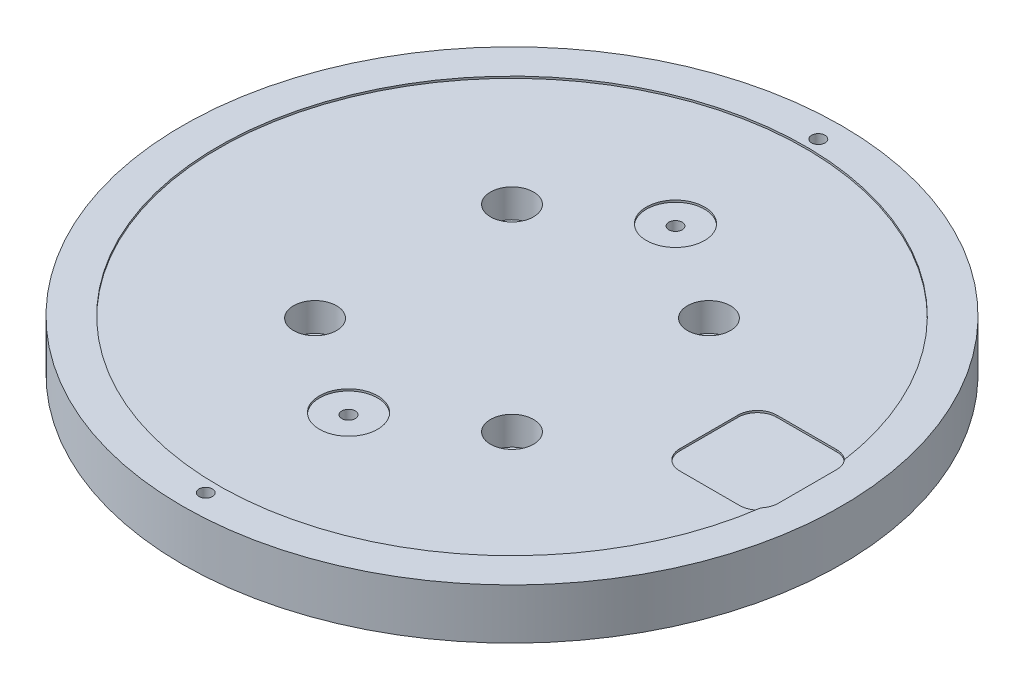
SolidWorks part; units mm, degrees
material "Plain Carbon Steel"
ref_plane "Front Plane" through (0, 0, 0) normal (0, 0, 1) x (1, 0, 0)
ref_plane "Top Plane" through (0, 0, 0) normal (0, 1, 0) x (1, 0, 0)
ref_plane "Right Plane" through (0, 0, 0) normal (1, 0, 0) x (0, 0, -1)
sketch "Sketch1" plane through (0, 0, 0) normal (0, 1, 0) x (1, 0, 0)
  circle A0 centre (0, 0) radius 75
  circle A1 centre (0, 0) radius 85
  dimension "D1" = 150
  dimension "D2" = 10
extrude "Boss-Extrude1" add sketch "Sketch1" against normal blind 13 contours A1
sketch "Sketch2" plane through (0, 0, 0) normal (0, 1, 0) x (1, 0, 0)
  circle A0 centre (0, 0) radius 75.75
  dimension "D1" = 151.5
extrude "Cut-Extrude1" cut sketch "Sketch2" against normal blind 0.5
sketch "Sketch3" plane through (0, -13, 0) normal (0, -1, 0) x (1, 0, 0)
  line L0 (-25.4, 0) -> (25.4, 0) construction
  line L1 (-25.4, -25.4) -> (25.4, -25.4)
  line L2 (-25.4, -25.4) -> (-25.4, 25.4)
  line L3 (-25.4, 25.4) -> (25.4, 25.4)
  line L4 (25.4, -25.4) -> (25.4, 25.4)
  line L5 (-25.4, -25.4) -> (25.4, 25.4) construction
  line L6 (-25.4, 25.4) -> (25.4, -25.4) construction
  point P0 (0, 0)
  point P6 (0, -79)
  point P7 (-25.4, 25.4)
  point P8 (25.4, 25.4)
  point P9 (25.4, -25.4)
  point P10 (-25.4, -25.4)
  point P13 (0, 79)
  dimension "D1" = 50.8
  dimension "D2" = 50.8
  dimension "D3" = 79
hole_wizard "CBORE for 1/4 Socket Head Cap Screw1" positions "Sketch4" profile "Sketch5" counterbore size "1/4" standard "ANSI Inch"
sketch "Sketch4" plane through (0, -0.5, 0) normal (0, -1, 0) x (-1, 0, 0)
  point P0 (25.4, -25.4)
  point P3 (-25.4, -25.4)
  point P6 (-25.4, 25.4)
  point P9 (25.4, 25.4)
sketch "Sketch5" plane through (-25.4, -0.5, 25.4) normal (1, 0, 0) x (0, 0, 1)
  line L0 (0, 0) -> (0, 17.0298)
  line L1 (0, 17.0298) -> (3.3782, 15)
  line L2 (3.3782, 15) -> (3.3782, 7.35)
  line L3 (3.3782, 7.35) -> (5.5562, 7.35)
  line L4 (5.5562, 7.35) -> (5.5563, 0)
  line L5 (5.5563, 0) -> (0, 0)
  line L10 (0, 17.0298) -> (-3.3782, 15) construction
  line L11 (0, -6.35) -> (0, 107.95) construction
  dimension "Hole Dia." = 6.7564
  dimension "Hole Depth" = 15
  dimension "C'Bore Dia." = 11.1125
  dimension "C'Bore Depth" = 7.35
  dimension "Drill Angle" = 118
hole_wizard "#8-32 Tapped Hole1" positions "Sketch6" profile "Sketch8" tap size "#8-32" standard "ANSI Inch"
sketch "Sketch6" plane through (0, 0, 0) normal (0, 1, 0) x (1, 0, 0)
  point P0 (0, 79)
  point P3 (0, -79)
sketch "Sketch8" plane through (0, 0, -79) normal (1, 0, 0) x (0, 0, 1)
  line L0 (0, 0) -> (0, 9.0378)
  line L1 (0, 9.0378) -> (1.7272, 8)
  line L2 (1.7272, 8) -> (1.7272, 0)
  line L5 (1.7272, 0) -> (0, 0)
  line L10 (0, 9.0378) -> (-1.7272, 8) construction
  line L11 (0, -6.35) -> (0, 107.95) construction
  dimension "Tap Drill Dia." = 3.4544
  dimension "Tap Drill Depth" = 8
  dimension "Drill Angle" = 118
cosmetic thread "Hole Thread3" parameters "D1"=5.5, "D2"=4.1656
cosmetic thread "Hole Thread4" parameters "D1"=5.5, "D2"=4.1656
sketch "Sketch9" plane through (0, 0, 0) normal (0, 1, 0) x (1, 0, 0)
  line L1 (76.2, -12.5) -> (50.8, -12.5)
  line L2 (76.2, -12.5) -> (76.2, 12.5)
  line L3 (76.2, 12.5) -> (50.8, 12.5)
  line L4 (50.8, -12.5) -> (50.8, 12.5)
  line L5 (76.2, -12.5) -> (50.8, 12.5) construction
  line L6 (76.2, 12.5) -> (50.8, -12.5) construction
  circle A0 centre (25.4, 25.4) radius 5.5562 construction
  circle A1 centre (25.4, -25.4) radius 5.5562 construction
  point P0 (63.5, 0)
  dimension "D1" = 25.4
  dimension "D2" = 25.4
  dimension "D3" = 25
  dimension "D4" = 12.9
extrude "wafer_tweezer_slot" cut sketch "Sketch9" against normal blind 1
fillet "Fillet1" radius 5 4 edges at (76.2, -0.5, -12.5) (76.2, -0.5, 12.5) (50.8, -0.75, 12.5) (50.8, -0.75, -12.5)
sketch "Sketch10" plane through (0, -0.5, 0) normal (0, 1, 0) x (1, 0, 0)
  circle A0 centre (0, -42.164) radius 7.5
  circle A1 centre (0, 42.164) radius 7.5
  dimension "D1" = 15
  dimension "D3" = 15
  dimension "D2" = 42.164
  dimension "D4" = 42.164
extrude "Cut-Extrude2" cut sketch "Sketch10" against normal blind 0.5
hole_wizard "#8-32 Tapped Hole2" positions "Sketch11" profile "Sketch12" tap size "#8-32" standard "ANSI Inch"
sketch "Sketch11" plane through (0, -1, 0) normal (0, 1, 0) x (1, 0, 0)
  point P2 (0, 42.164)
  point P7 (0, -42.164)
sketch "Sketch12" plane through (0, -1, -42.164) normal (1, 0, 0) x (0, 0, 1)
  line L0 (0, 0) -> (0, 9.0378)
  line L1 (0, 9.0378) -> (1.7272, 8)
  line L2 (1.7272, 8) -> (1.7272, 0)
  line L5 (1.7272, 0) -> (0, 0)
  line L10 (0, 9.0378) -> (-1.7272, 8) construction
  line L11 (0, -6.35) -> (0, 107.95) construction
  dimension "Tap Drill Dia." = 3.4544
  dimension "Tap Drill Depth" = 8
  dimension "Drill Angle" = 118
cosmetic thread "Hole Thread1" parameters "D1"=5.5, "D2"=4.1656
cosmetic thread "Hole Thread2" parameters "D1"=5.5, "D2"=4.1656
